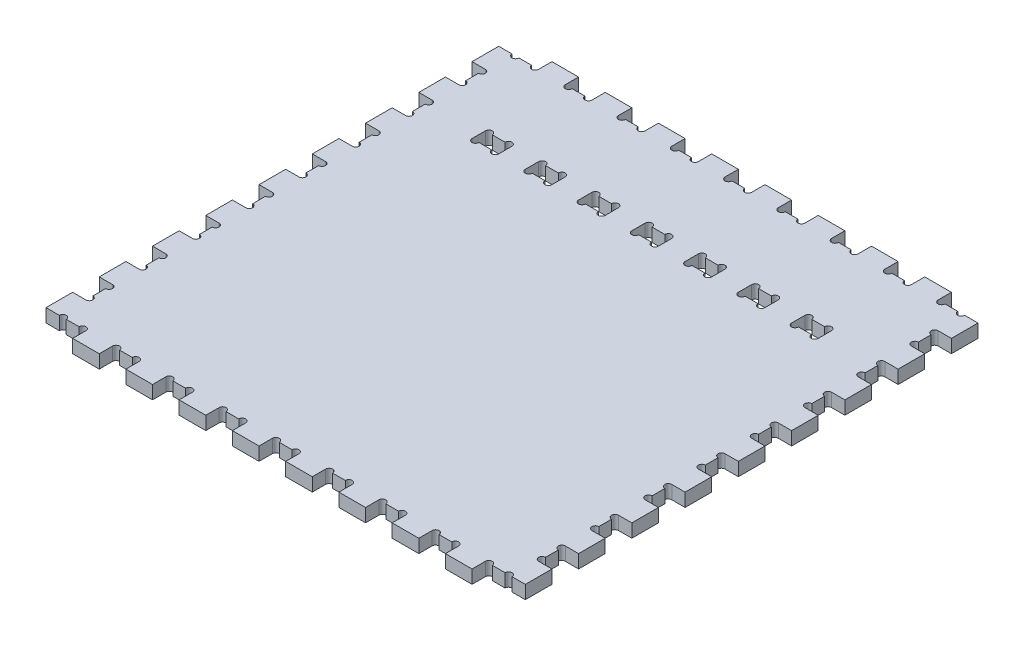
SolidWorks part; units mm, degrees
ref_plane "Front Plane" through (0, 0, 0) normal (0, 0, 1) x (1, 0, 0)
ref_plane "Top Plane" through (0, 0, 0) normal (0, 1, 0) x (1, 0, 0)
ref_plane "Right Plane" through (0, 0, 0) normal (1, 0, 0) x (0, 0, -1)
sketch "Sketch1" plane through (0, 0, 0) normal (0, 1, 0) x (1, 0, 0)
  line L1 (228.6, -228.6) -> (-228.6, -228.6)
  line L2 (228.6, -228.6) -> (228.6, 228.6)
  line L3 (228.6, 228.6) -> (-228.6, 228.6)
  line L4 (-228.6, -228.6) -> (-228.6, 228.6)
  line L5 (228.6, -228.6) -> (-228.6, 228.6) construction
  line L6 (228.6, 228.6) -> (-228.6, -228.6) construction
  point P0 (0, 0)
  dimension "D1" = 457.2
  dimension "D2" = 457.2
extrude "Boss-Extrude1" add sketch "Sketch1" along normal blind 12.7
sketch "Sketch2" plane through (0, 12.7, 0) normal (0, 1, 0) x (1, 0, 0)
  line L0 (228.6, 228.6) -> (-228.6, 228.6) construction
  line L1 (-215.9, 228.6) -> (-190.5, 228.6)
  line L2 (-215.9, 228.6) -> (-215.9, 215.9)
  line L3 (-215.9, 215.9) -> (-190.5, 215.9)
  line L4 (-190.5, 228.6) -> (-190.5, 215.9)
  line L5 (-215.9, 215.9) -> (-228.6, 215.9) construction
  line L6 (-228.6, 228.6) -> (-228.6, -228.6) construction
  circle A0 centre (-212.598, 215.9) radius 3.302
  circle A1 centre (-193.802, 215.9) radius 3.302
  line M8 (228.6, 228.6) -> (-228.6, 228.6)
  dimension "D3" = 6.604
  dimension "D4" = 6.604
  dimension "D1" = 25.4
  dimension "D2" = 12.7
  dimension "D5" = 12.7
extrude "Cut-Extrude1" cut sketch "Sketch2" against normal blind 12.7 contours A1 L4 L2 A0 L3 M8 | L3 A0 | L3 A1 | L3 A1 | L3 A0 region at (-203.2, 12.7, -222.8379) region at (-212.598, 12.7, -217.3014) region at (-212.598, 12.7, -214.4986) region at (-193.802, 12.7, -214.4986) region at (-193.802, 12.7, -217.3014)
pattern_linear "LPattern1" count 9 spacing 50.8 along (1, 0, 0) of "Cut-Extrude1"
ref_plane "Plane1" through (0, 0, 0) normal (0, 0, -1) x (-1, 0, 0)
ref_plane "Plane2" through (0, 0, 0) normal (-1, 0, 0) x (0, 0, 1)
mirror "Mirror1" about plane through (0, 0, 0) normal (0, 0, -1) of "LPattern1"
sketch "Sketch3" plane through (0, 12.7, 0) normal (0, 1, 0) x (1, 0, 0)
  line L1 (-228.6, 228.6) -> (-215.9, 228.6)
  line L2 (-228.6, 228.6) -> (-228.6, 215.9)
  line L3 (-228.6, 215.9) -> (-215.9, 215.9)
  line L4 (-215.9, 228.6) -> (-215.9, 215.9)
extrude "Cut-Extrude2" cut sketch "Sketch3" against normal through all
mirror "Mirror2" about plane through (0, 0, 0) normal (-1, 0, 0) of "Cut-Extrude2"
mirror "Mirror3" about plane through (0, 0, 0) normal (0, 0, -1) of "Mirror2"
sketch "Sketch4" plane through (0, 12.7, 0) normal (0, 1, 0) x (1, 0, 0)
  line L0 (-228.6, 215.9) -> (-228.6, -215.9) construction
  line L1 (-228.6, 190.5) -> (-215.9, 190.5)
  line L2 (-228.6, 190.5) -> (-228.6, 165.1)
  line L3 (-228.6, 165.1) -> (-215.9, 165.1)
  line L4 (-215.9, 190.5) -> (-215.9, 165.1)
  line L5 (-215.9, 190.5) -> (-186.3664, 190.5) construction
  line L6 (-186.3664, 190.5) -> (-186.3664, 228.6) construction
  line L7 (-165.1, 228.6) -> (-190.5, 228.6) construction
  circle A0 centre (-215.9, 187.198) radius 3.302
  circle A1 centre (-215.9, 168.402) radius 3.302
  dimension "D3" = 6.604
  dimension "D4" = 6.604
  dimension "D1" = 12.7
  dimension "D2" = 25.4
  dimension "D5" = 38.1
extrude "Cut-Extrude3" cut sketch "Sketch4" against normal through all contours A1 L4 A0 L1 L2 L3 | L4 A0 | L4 A1 | L4 A1 | L4 A0 region at (-222.8379, 12.7, -177.8) region at (-214.4986, 12.7, -187.198) region at (-217.3014, 12.7, -187.198) region at (-217.3014, 12.7, -168.402) region at (-214.4986, 12.7, -168.402)
pattern_linear "LPattern2" count 9 spacing 50.8 along (0, 0, 1) of "Cut-Extrude3"
mirror "Mirror4" about plane through (0, 0, 0) normal (-1, 0, 0) of "LPattern2"
sketch "Sketch5" plane through (0, 12.7, 0) normal (0, 1, 0) x (1, 0, 0)
  line L1 (-165.1, 139.7) -> (-139.7, 139.7)
  line L2 (-165.1, 139.7) -> (-165.1, 127)
  line L3 (-165.1, 127) -> (-139.7, 127)
  line L4 (-139.7, 139.7) -> (-139.7, 127)
  line L6 (-165.1, 215.9) -> (-165.1, 139.7) construction
  circle A0 centre (-161.798, 139.7) radius 3.302
  circle A1 centre (-143.002, 139.7) radius 3.302
  circle A2 centre (-161.798, 127) radius 3.302
  circle A3 centre (-143.002, 127) radius 3.302
  point P12 (0, 0)
  dimension "D3" = 6.604
  dimension "D1" = 12.7
  dimension "D2" = 25.4
  dimension "D4" = 76.2
extrude "Cut-Extrude4" cut sketch "Sketch5" against normal through all contours A3 L4 A1 L1 A0 L2 A2 L3 | L1 A0 | L1 A0 | L3 A2 | L3 A2 | L3 A3 | L3 A3 | A1 region at (-161.798, 12.7, -141.1014) region at (-152.4, 12.7, -133.35) region at (-161.798, 12.7, -138.2986) region at (-161.798, 12.7, -128.4014) region at (-161.798, 12.7, -125.5986) region at (-143.002, 12.7, -128.4014) region at (-143.002, 12.7, -125.5986)
pattern_linear "LPattern3" count 7 spacing 50.8 along (1, 0, 0) of "Cut-Extrude4"
